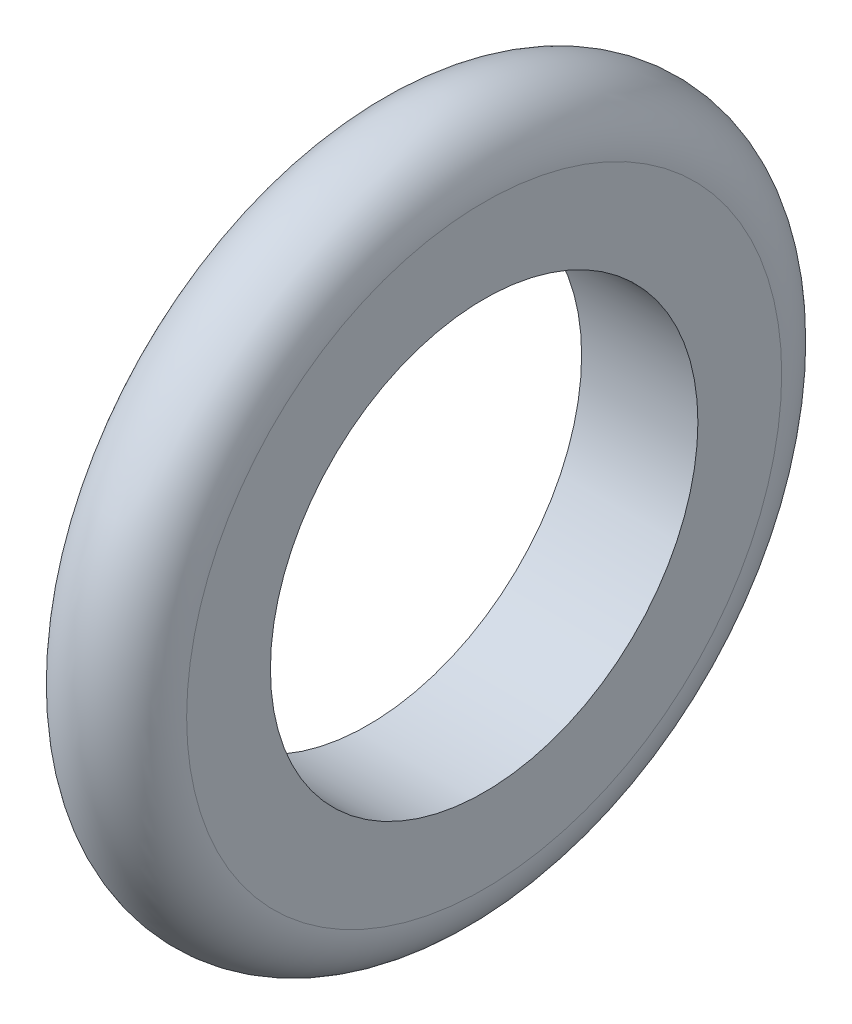
SolidWorks part; units mm, degrees
ref_plane "Front Plane" through (0, 0, 0) normal (0, 0, 1) x (1, 0, 0)
ref_plane "Top Plane" through (0, 0, 0) normal (0, 1, 0) x (1, 0, 0)
ref_plane "Right Plane" through (0, 0, 0) normal (1, 0, 0) x (0, 0, -1)
sketch "Sketch1" plane through (0, 0, 0) normal (1, 0, 0) x (0, 0, -1)
  circle A0 centre (0, 0) radius 3.9688
  circle A1 centre (0, 0) radius 6.604
  dimension "D1" = 7.9375
  dimension "D2" = 13.208
extrude "Boss-Extrude1" add sketch "Sketch1" along normal blind 2.159
fillet "Fillet1" 2 edges at (0, 0, -6.604) (2.159, 0, -6.604) type full round first side face at (0, 0, -6.604) second side face at (2.159, 0, -6.604) middle face at (2.159, 0, -6.604)
